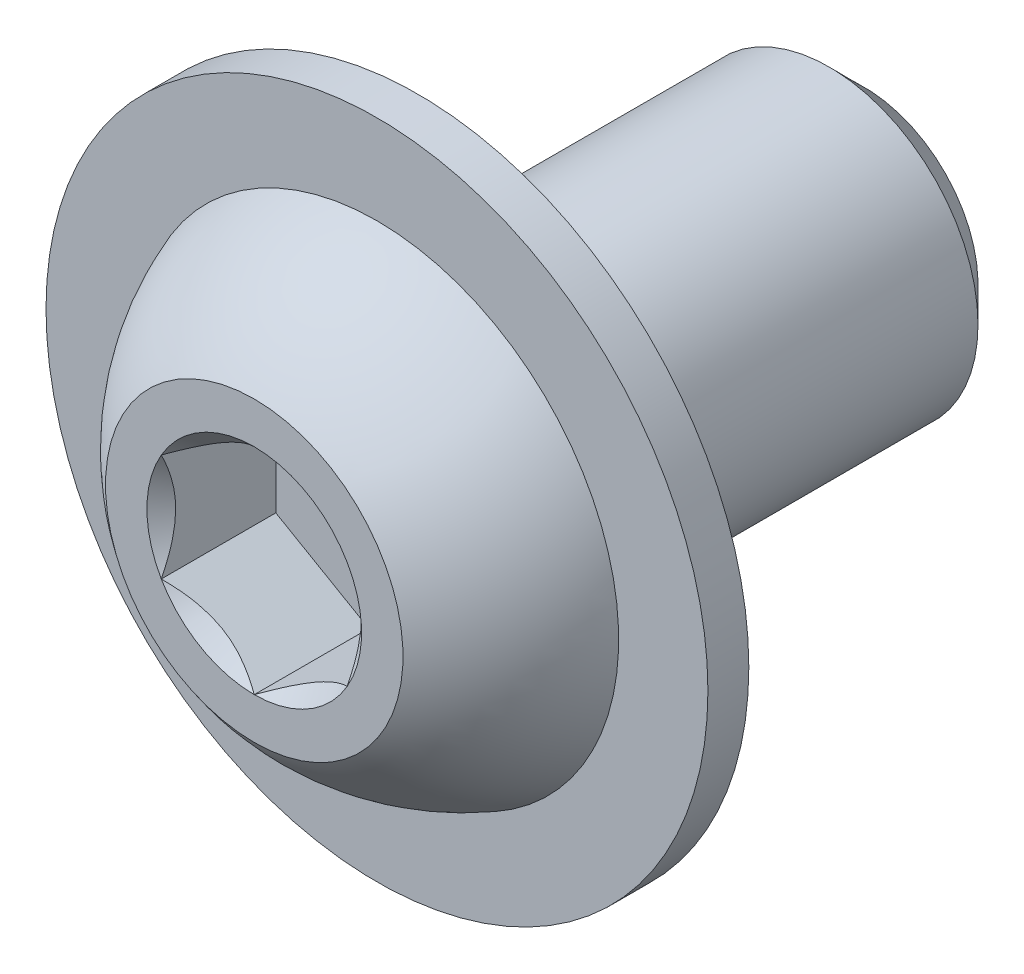
SolidWorks part; units mm, degrees
material "AISI 304"
ref_plane "Front" through (0, 0, 0) normal (0, 0, 1) x (1, 0, 0)
ref_plane "Top" through (0, 0, 0) normal (0, 1, 0) x (1, 0, 0)
ref_plane "Right" through (0, 0, 0) normal (1, 0, 0) x (0, 0, -1)
sketch "Sketch1" plane through (0, 0, 0) normal (1, 0, 0) x (0, 0, -1)
  line L2 (4.4, 4) -> (16.4, 4)
  line L3 (16.4, 4) -> (16.4, 0)
  line L4 (16.4, 0) -> (4.4, 0)
  line L6 (3.3, 6.5) -> (4.4, 6.5) construction
  line L7 (16.4, 4) -> (16.4, -4) construction
  line L8 (0, 0) -> (4.4, 0) construction
  line L9 (4.4, 6.5) -> (4.4, -6.5) construction
  line L11 (4.4, 4) -> (4.4, 0)
  line L13 (0, 2.5) -> (0, -2.5) construction
  line L14 (0, 2.5) -> (0, 4) construction
  line L15 (3.3, 6.5) -> (3.3, 8.9) construction
  line L16 (3.3, 8.9) -> (4.4, 8.9) construction
  line L17 (4.4, 8.9) -> (4.4, 6.5) construction
  line L18 (4.4, 8.9) -> (4.4, -8.9) construction
  arc A3 (0, 4) -> (3.3, 6.5) centre (5.6273, 0) cw construction
  dimension "D1" = 1.1
revolve "Revolve1" add sketch "Sketch1" angle 360 mid plane about L4
sketch "Sketch3" plane through (0, 0, -16.4) normal (0, 0, -1) x (-1, 0, 0)
  circle A0 centre (0, 0) radius 4
curve "Helix/Spiral1" pitch 1.25 height 13.25 turns 10.6
sketch "Sketch2" plane through (0, 0, 0) normal (1, 0, 0) x (0, 0, -1)
  line L0 (16.4, 4) -> (17.4937, 4)
  line L1 (17.4937, 4) -> (17.025, 3.1881)
  line L2 (17.025, 3.1881) -> (16.8687, 3.1881)
  line L3 (16.8687, 3.1881) -> (16.4, 4)
  line L4 (16.6344, 3.5941) -> (17.2594, 3.5941) construction
  dimension "D1" = 60
  dimension "D2" = 0.1562
  dimension "D3" = 0.625
chamfer "Chamfer1" distance 0.9375 angle 45 1 edges at (0, 4, -16.4)
sweep "Cut-Sweep1" [suppressed] cut profiles "Sketch2" path "Helix/Spiral1"
sketch "Sketch7" plane through (0, 0, 0) normal (1, 0, 0) x (0, 0, -1)
  line L6 (3.3, 6.5) -> (4.4, 6.5) construction
  line L8 (0, 0) -> (4.4, 0) construction
  line L11 (4.4, 6.5) -> (4.4, -6.5) construction
  line L12 (3.3, 6.5) -> (4.4, 6.5)
  line L13 (0, 0) -> (4.4, 0)
  line L14 (0, 2.5) -> (0, -2.5) construction
  line L15 (4.4, 6.5) -> (4.4, 0)
  line L16 (0, 4) -> (0, 0)
  arc A2 (3.3, 6.5) -> (0, 4) centre (5.6273, 0) ccw construction
  arc A3 (3.3, 6.5) -> (0, 4) centre (5.6273, 0) ccw
revolve "Revolve2" add sketch "Sketch7" angle 360 mid plane about L13
sketch "Sketch11" plane through (0, 0, -4.4) normal (0, 0, -1) x (-1, 0, 0)
  circle A0 centre (0, 0) radius 8.9
extrude "Boss-Extrude3" add sketch "Sketch11" against normal up to vertex (1.1 mm away) up to point (0, 6.5, -3.3)
sketch "Sketch5" plane through (0, 0, 0) normal (0, 0, 1) x (1, 0, 0)
  line L1 (2.5, -1.4434) -> (2.5, 1.4434)
  line L2 (2.5, 1.4434) -> (0, 2.8868)
  line L3 (0, 2.8868) -> (-2.5, 1.4434)
  line L4 (-2.5, 1.4434) -> (-2.5, -1.4434)
  line L5 (-2.5, -1.4434) -> (0, -2.8868)
  line L6 (0, -2.8868) -> (2.5, -1.4434)
  circle A0 centre (0, 0) radius 2.5 construction
extrude "Cut-Extrude2" cut sketch "Sketch5" against normal blind 3.08
sketch "Sketch6" plane through (0, 0, 0) normal (0, 0, 1) x (1, 0, 0)
  circle A0 centre (0, 0) radius 2.8868
extrude "Cut-Extrude3" cut sketch "Sketch6" against normal blind 3.08 draft 45
sketch "Sketch9" [suppressed] plane through (0, 0, -4.4) normal (0, 0, 1) x (1, 0, 0)
  circle A2 centre (0, 0) radius 4
extrude "Boss-Extrude2" [suppressed] add sketch "Sketch9" against normal offset from surface (6.35 mm away) 31.75 up to face at (0, 3.0625, -16.4)
sketch "Sketch10" plane through (0, 0, 0) normal (1, 0, 0) x (0, 0, -1)
  line L0 (16.4, 4) -> (16.4, -4) construction
  point P0 (14.525, -4)
  dimension "D1" = 1.875
equation "\"D3@Helix/Spiral1\" = \"Lg@Sketch1\" + \"D4@Helix/Spiral1\""
equation "\"D2@Sketch2\" = \"D4@Helix/Spiral1\" * .125"
equation "\"D3@Sketch2\" = \"D4@Helix/Spiral1\" * .5"
equation "\"D1@Chamfer1\" = \"D4@Helix/Spiral1\" * .75"
equation "\"D1@Cut-Extrude2\" = \"Head Ht@Sketch1\" * .7"
equation "\"D1@Sketch1\" = \"Head Ht@Sketch1\" * .25"
equation "\"D1@Sketch10\" = \"D4@Helix/Spiral1\" * 1.5"
equation "\"D1@Cut-Extrude3\" = \"D1@Cut-Extrude2\""
